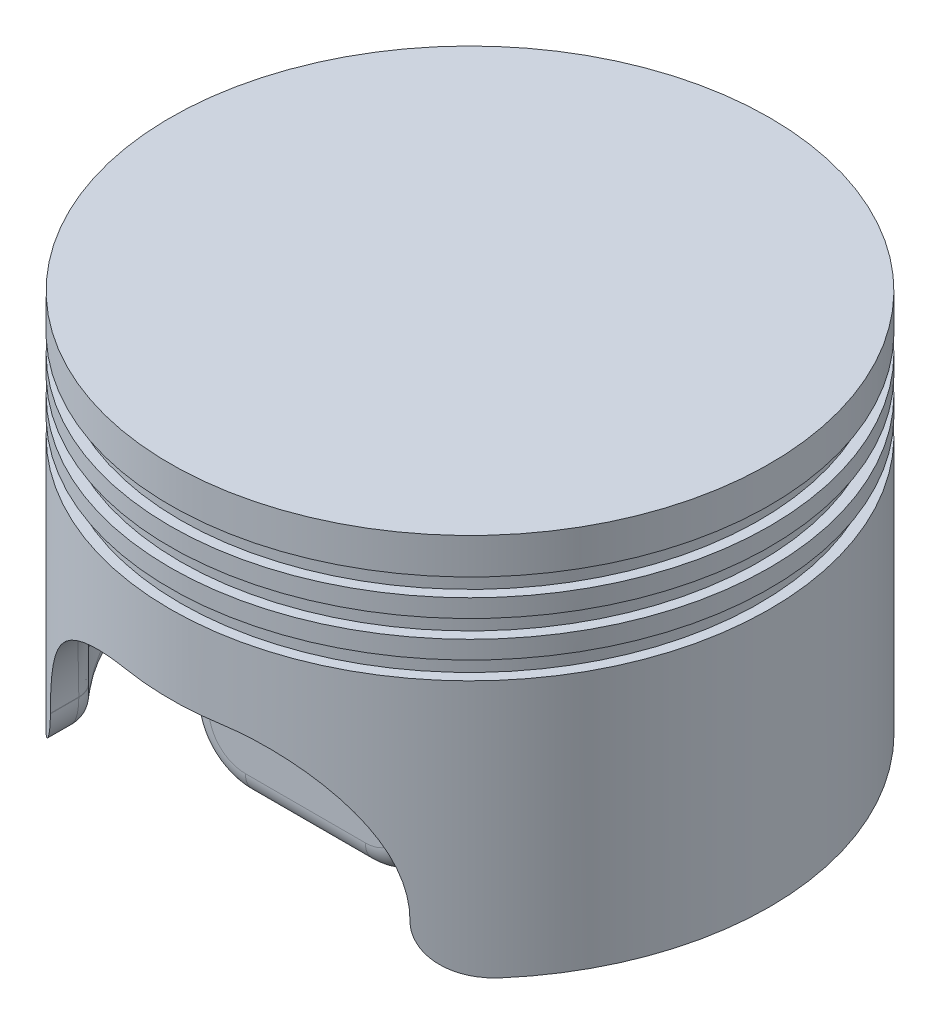
SolidWorks part; units mm, degrees
ref_plane "Front Plane" through (0, 0, 0) normal (0, 0, 1) x (1, 0, 0)
ref_plane "Top Plane" through (0, 0, 0) normal (0, 1, 0) x (1, 0, 0)
ref_plane "Right Plane" through (0, 0, 0) normal (1, 0, 0) x (0, 0, -1)
sketch "Sketch1" plane through (0, 0, 0) normal (1, 0, 0) x (0, 0, -1)
  line L0 (0, 0) -> (63.5, 0)
  line L1 (63.5, 0) -> (63.5, -81.28)
  line L2 (63.5, -81.28) -> (57.15, -81.28)
  line L3 (57.15, -81.28) -> (57.15, -19)
  line L4 (57.15, -19) -> (0, -19)
  line L5 (0, -19) -> (0, 0)
  dimension "D1" = 63.5
  dimension "D2" = 81.28
  dimension "D3" = 6.35
  dimension "D4" = 19
revolve "Revolve1" add sketch "Sketch1" angle 360 about L5
sketch "Sketch2" plane through (0, 0, 0) normal (0, 0, 1) x (1, 0, 0)
  line L0 (63.8664, -7.62) -> (61.3264, -7.62)
  line L1 (61.3264, -7.62) -> (61.3264, -11.43)
  line L2 (61.3264, -11.43) -> (63.8664, -11.43)
  line L3 (63.8664, -11.43) -> (63.8664, -7.62)
  line L4 (63.5, 0) -> (-63.5, 0) construction
  line L5 (0, 43.217) -> (0, -30.6195) construction
  dimension "D1" = 7.62
  dimension "D2" = 3.81
  dimension "D3" = 2.54
revolve "Cut-Revolve1" cut sketch "Sketch2" angle 360 about L5
ref_axis "Axis1" through (0, 71.9657, 0) along (0, -1, 0)
pattern_linear "LPattern1" count 3 spacing 7.62 along (0, -1, 0) of "Cut-Revolve1"
sketch "Sketch3" plane through (0, 0, 0) normal (0, 0, 1) x (1, 0, 0)
  line L0 (0, 71.9657) -> (0, -113.2334) construction
  line L1 (-38.1, -43.18) -> (38.1, -43.18)
  line L2 (-38.1, -43.18) -> (-38.1, -81.28)
  line L3 (-38.1, -81.28) -> (38.1, -81.28)
  line L4 (38.1, -43.18) -> (38.1, -81.28)
  line L5 (-38.1, -43.18) -> (38.1, -81.28) construction
  line L6 (-38.1, -81.28) -> (38.1, -43.18) construction
  line L7 (-57.15, -81.28) -> (57.15, -81.28) construction
  point P0 (0, -62.23)
  dimension "D1" = 76.2
  dimension "D2" = 38.1
extrude "Cut-Extrude1" cut sketch "Sketch3" against normal through all both and the other way through all
fillet "Fillet1" radius 28 4 edges at (38.1, -43.18, -46.6985) (-38.1, -43.18, -46.6985) (-38.1, -43.18, 46.6985) (38.1, -43.18, 46.6985)
sketch "Sketch5" plane through (0, -19, 0) normal (0, -1, 0) x (1, 0, 0)
  line L1 (-25.4, 15.88) -> (25.4, 15.88)
  line L2 (-25.4, 15.88) -> (-25.4, 34.88)
  line L3 (-25.4, 34.88) -> (25.4, 34.88)
  line L4 (25.4, 15.88) -> (25.4, 34.88)
  line L5 (-25.4, 15.88) -> (25.4, 34.88) construction
  line L6 (-25.4, 34.88) -> (25.4, 15.88) construction
  point P0 (0, 25.38)
  dimension "D1" = 50.8
  dimension "D2" = 19
  dimension "D3" = 15.88
extrude "Boss-Extrude2" add sketch "Sketch5" along normal blind 63.5
mirror "Mirror2" about plane through (0, 0, 0) normal (0, 0, 1) of "Boss-Extrude2"
sketch "Sketch6" plane through (0, 0, 34.88) normal (0, 0, 1) x (1, 0, 0)
  line L0 (25.4, -82.5) -> (-25.4, -82.5) construction
  circle A0 centre (0, -57.1) radius 12.7
  dimension "D2" = 25.4
  dimension "D1" = 25.4
extrude "Cut-Extrude2" cut sketch "Sketch6" against normal through all
fillet "Fillet2" radius 12.7 4 edges at (-25.4, -82.5, 25.38) (25.4, -82.5, 25.38) (25.4, -82.5, -25.38) (-25.4, -82.5, -25.38)
fillet "Fillet3" radius 10 4 edges at (-38.1, -81.28, 46.6985) (-38.1, -81.28, -46.6985) (38.1, -81.28, 46.6985) (38.1, -81.28, -46.6985)
fillet "Fillet4" radius 5 37 edges at (-25.4, -44.4, -15.88) (-21.6803, -78.7803, -15.88) (25.4, -44.4, -15.88) (21.6803, -78.7803, -15.88) (25.4, -44.4, -34.88) (21.6803, -78.7803, -34.88) (-25.4, -44.4, -34.88) (-21.6803, -78.7803, -34.88) (-25.4, -44.4, 15.88) (-21.6803, -78.7803, 15.88) (25.4, -44.4, 15.88) (21.6803, -78.7803, 15.88) (25.4, -44.4, 34.88) (21.6803, -78.7803, 34.88) (-25.4, -44.4, 34.88) (-21.6803, -78.7803, 34.88) (39.4335, -76.2692, -41.3657) (38.1, -71.23, -42.5971) (26.8841, -48.7681, -50.4318) (0, -43.18, -57.15) (-33.8387, -56.3316, -46.055) (-38.1, -71.23, -42.5971) (-40.816, -78.1316, -40.0022) (-57.15, -81.28, 0) (-39.4335, -76.2692, 41.3657) (-38.1, -71.23, 42.5971) (-26.8841, -48.7681, 50.4318) (0, -43.18, 57.15) (33.8387, -56.3316, 46.055) (38.1, -71.23, 42.5971) (40.816, -78.1316, 40.0022) (0, -82.5, -15.88) (0, -82.5, -34.88) (0, -82.5, 15.88) (0, -82.5, 34.88) (0, -19, -57.15) (57.15, -81.28, 0)
